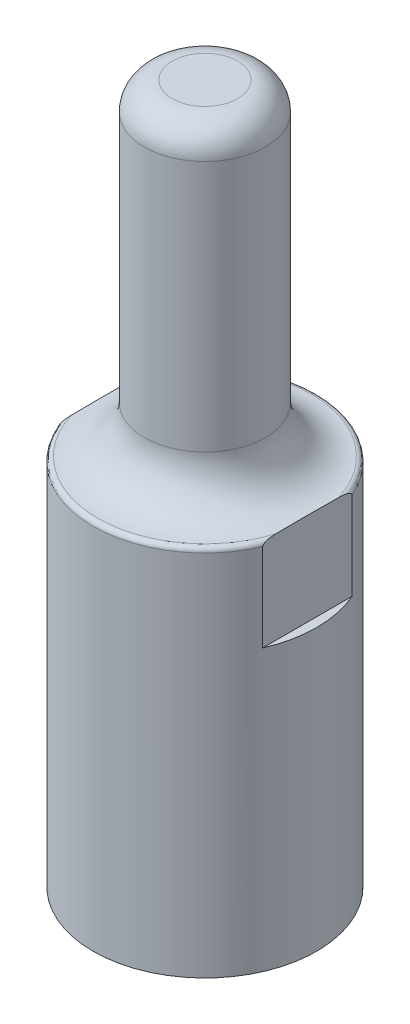
SolidWorks part; units mm, degrees
material "1060 Alloy"
ref_plane "Front Plane" through (0, 0, 0) normal (0, 0, 1) x (1, 0, 0)
ref_plane "Top Plane" through (0, 0, 0) normal (0, 1, 0) x (1, 0, 0)
ref_plane "Right Plane" through (0, 0, 0) normal (1, 0, 0) x (0, 0, -1)
sketch "Sketch1" plane through (0, 0, 0) normal (0, 1, 0) x (1, 0, 0)
  circle A0 centre (0, 0) radius 12
  dimension "D1" = 24
extrude "Boss-Extrude1" add sketch "Sketch1" along normal blind 40
sketch "Sketch2" plane through (0, 40, 0) normal (0, 1, 0) x (1, 0, 0)
  circle A0 centre (0, 0) radius 6.5
  dimension "D1" = 13
extrude "Boss-Extrude2" add sketch "Sketch2" along normal blind 35
fillet "Fillet1" radius 3 1 edges at (0, 75, 6.5)
fillet "Fillet2" radius 5 1 edges at (0, 40, 6.5)
fillet "Fillet3" radius 0.5 1 edges at (0, 40, 12)
sketch "Sketch3" plane through (0, 0, 0) normal (0, 0, 1) x (1, 0, 0)
  line L11 (-12, 39.5) -> (-12, 0) construction
  line L12 (-12, 30.0974) -> (-11, 30.0974)
  line L13 (-12, 30.0974) -> (-12, 40.0974)
  line L14 (-12, 40.0974) -> (-11, 40.0974)
  line L15 (-11, 30.0974) -> (-11, 40.0974)
  line L16 (0, -13.2) -> (0, 13.2) construction
  line L17 (11, 30.0974) -> (11, 40.0974)
  line L18 (12, 40.0974) -> (11, 40.0974)
  line L19 (12, 30.0974) -> (12, 40.0974)
  line L20 (12, 30.0974) -> (11, 30.0974)
  dimension "D1" = 10
  dimension "D2" = 1
extrude "Cut-Extrude1" cut sketch "Sketch3" against normal through all both and the other way through all
sketch "Sketch4" plane through (0, 0, 0) normal (0, -1, 0) x (1, 0, 0)
  circle A0 centre (0, 0) radius 4
extrude "Cut-Extrude2" cut sketch "Sketch4" against normal blind 5
